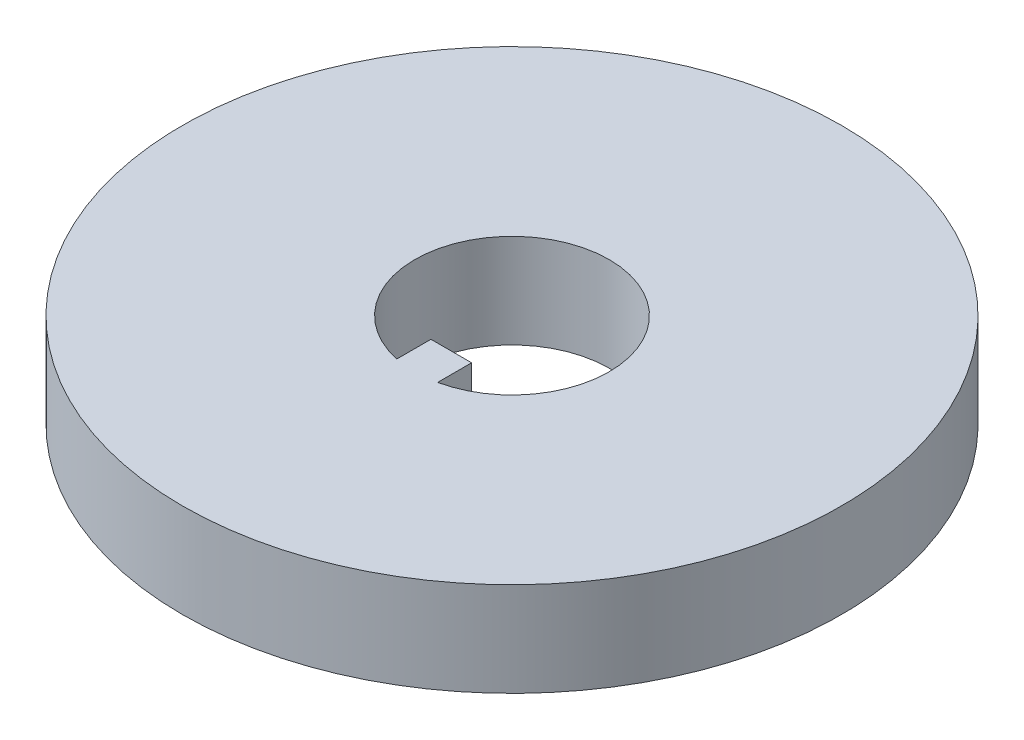
SolidWorks part; units mm, degrees
ref_plane "Front Plane" through (0, 0, 0) normal (0, 0, 1) x (1, 0, 0)
ref_plane "Top Plane" through (0, 0, 0) normal (0, 1, 0) x (1, 0, 0)
ref_plane "Right Plane" through (0, 0, 0) normal (1, 0, 0) x (0, 0, -1)
sketch "Sketch1" plane through (0, 0, 0) normal (0, 1, 0) x (1, 0, 0)
  line L1 (-3.1973, -9.723) -> (3.2847, -9.723)
  line L2 (-3.1973, -9.723) -> (-3.1973, -20.6925)
  line L3 (-3.1973, -20.6925) -> (3.2847, -20.6925)
  line L4 (3.2847, -9.723) -> (3.2847, -20.6925)
  circle A0 centre (0, 0) radius 52.5246
  circle A1 centre (0, 0) radius 15.4936
extrude "Boss-Extrude1" add sketch "Sketch1" along normal blind 15 contours L2 A1 L4 L1 | A0 A1 L4 L3 L2 | A1 L2 L3 L4 region at (0.0419, 0, 12.5523) region at (0.0456, 0, 18.0352) region at (-51.039, 0, 0)
